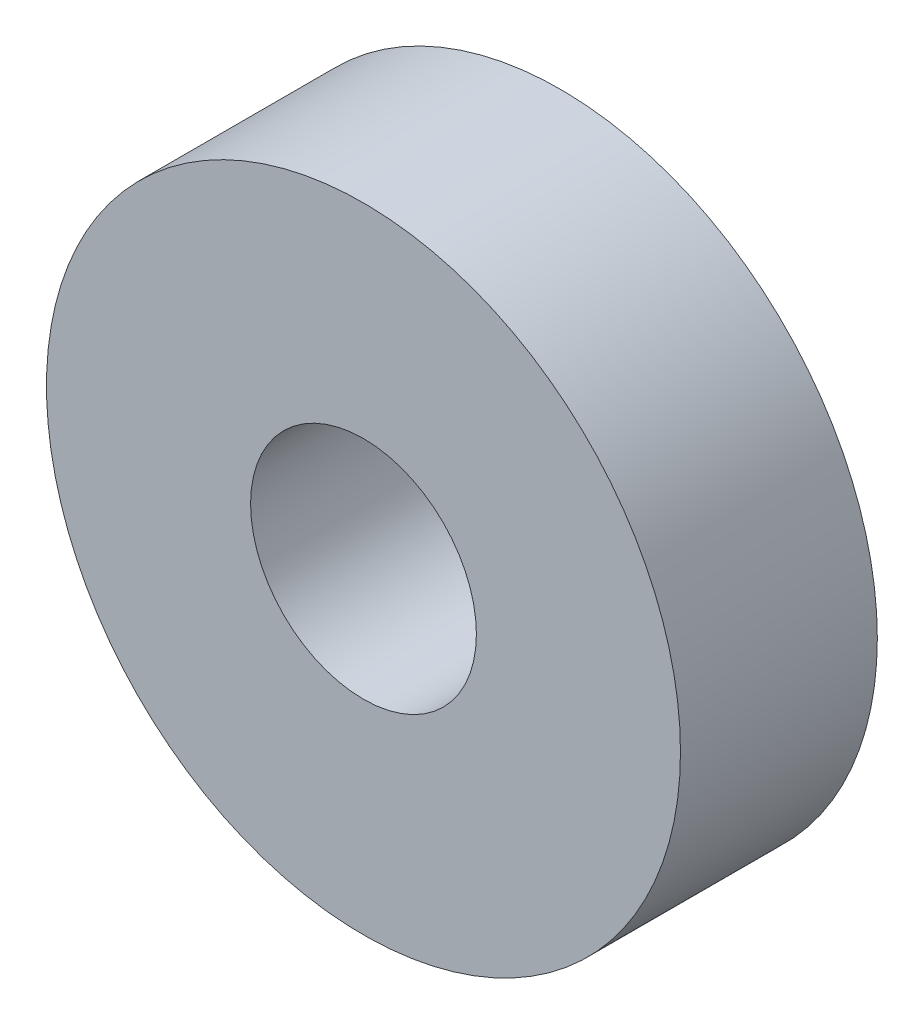
SolidWorks part; units mm, degrees
ref_plane "Front Plane" through (0, 0, 0) normal (0, 0, 1) x (1, 0, 0)
ref_plane "Top Plane" through (0, 0, 0) normal (0, 1, 0) x (1, 0, 0)
ref_plane "Right Plane" through (0, 0, 0) normal (1, 0, 0) x (0, 0, -1)
sketch "Sketch1" plane through (0, 0, 0) normal (0, 0, 1) x (1, 0, 0)
  circle A0 centre (0, 0) radius 10.95
  circle A1 centre (0, 0) radius 5.85
  circle A2 centre (0, 0) radius 3.9
  dimension "D1" = 21.9
  dimension "D2" = 11.7
  dimension "D3" = 7.8
extrude "Boss-Extrude1" add sketch "Sketch1" along normal blind 3.4 and the other way blind 3.4 contours A0 A1 | A1 A2 region at (-10.6403, 0, 0) region at (-5.6845, 0, 0)
